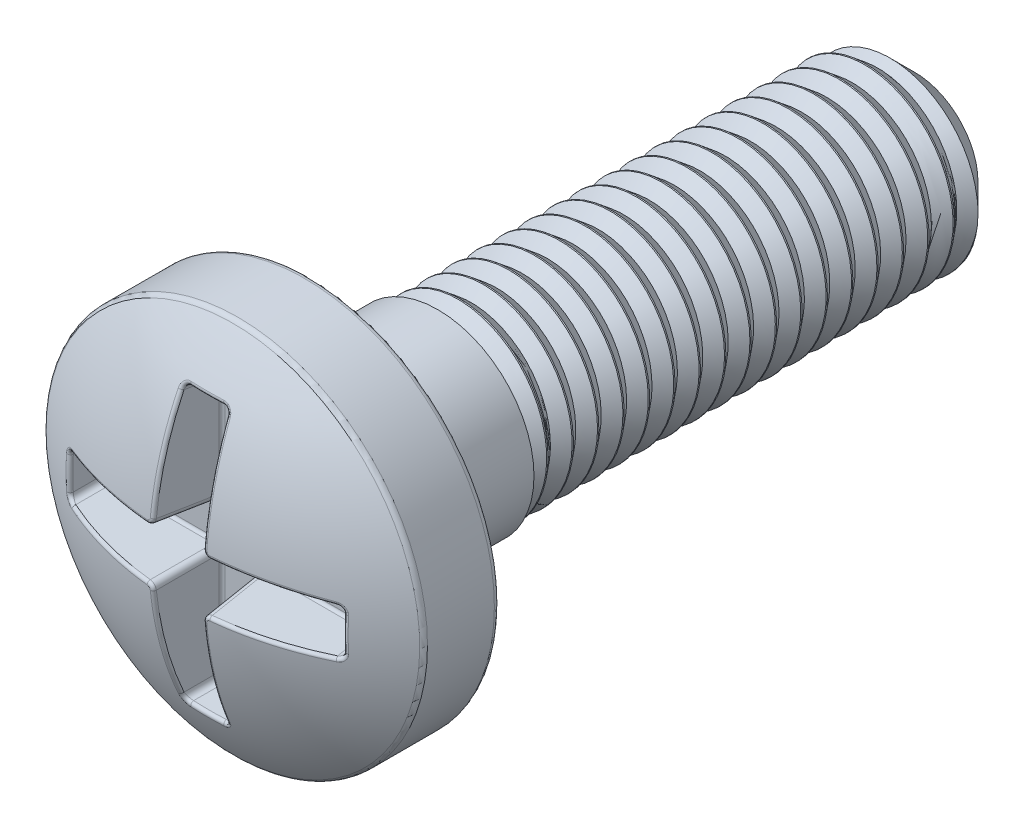
SolidWorks part; units mm, degrees
material "Cast Stainless Steel"
ref_plane "Front Plane" through (0, 0, 0) normal (0, 0, 1) x (1, 0, 0)
ref_plane "Top Plane" through (0, 0, 0) normal (0, 1, 0) x (1, 0, 0)
ref_plane "Right Plane" through (0, 0, 0) normal (1, 0, 0) x (0, 0, -1)
sketch "Sketch1" plane through (0, 0, 0) normal (1, 0, 0) x (0, 0, -1)
  line L0 (18.4658, 0) -> (18.4658, 2.4003)
  line L1 (0, 0) -> (18.4658, 0) construction
  line L2 (0, 0) -> (18.4658, 0)
  line L3 (18.4658, 2.4003) -> (3.3782, 2.4003)
  line L4 (3.3782, 2.4003) -> (3.3782, 4.7371)
  line L5 (3.3782, 4.7371) -> (1.4732, 4.7371)
  line L6 (0, 0) -> (0, -1.4058) construction
  arc A0 (0, 0) -> (1.4732, 4.7371) centre (8.3527, 0) cw
  dimension "D1" = 3.3782
  dimension "D2" = 9.4742
  dimension "D3" = 4.8006
  dimension "D4" = 1.905
  dimension "D5" = 15.0876
revolve "Revolve1" add sketch "Sketch1" angle 360 about L2
chamfer "Chamfer1" distance 0.8128 angle 45 1 edges at (2.4003, 0, -18.4658)
ref_plane "Plane1" through (0, 0, -6.5532) normal (0, 0, -1) x (-1, 0, 0)
sketch "Sketch2" plane through (0, 0, -6.5532) normal (0, 0, -1) x (-1, 0, 0)
  circle A0 centre (0, 0) radius 3.0006
  circle A2 centre (0, 0) radius 2.2733
  circle A3 centre (0, 0) radius 2.2733
  dimension "D1" = 0.127
extrude "Extrude1" cut sketch "Sketch2" along normal blind 14.224
sketch "Sketch3" plane through (0, 0, -6.5532) normal (0, 0, -1) x (-1, 0, 0)
  circle A0 centre (0, 0) radius 2.2733 construction
  circle A1 centre (0, 0) radius 2.2733
curve "Helix/Spiral1" pitch 0.635 height 12.3825 turns 19.5
sketch "Sketch4" plane through (0, 0, 0) normal (1, 0, 0) x (0, 0, -1)
  line L0 (6.5532, 2.2733) -> (6.8543, 2.0312)
  line L1 (6.8543, 2.0312) -> (7.1553, 2.2733)
  line L2 (17.78, 2.2733) -> (6.5532, 2.2733) construction
  line L3 (7.1553, 2.2733) -> (6.5532, 2.2733)
  line L4 (17.78, 2.2733) -> (6.5532, 2.2733) construction
sweep "Cut-Sweep1" cut profiles "Sketch4" path "Helix/Spiral1"
sketch "Sketch5" plane through (0, 0, -6.5532) normal (0, 0, -1) x (-1, 0, 0)
  circle A0 centre (0, 0) radius 2.4003 construction
  circle A1 centre (0, 0) radius 2.4003
extrude "Extrude2" add sketch "Sketch5" against normal blind 2.54
sketch "Sketch6" plane through (0, 0, 0) normal (0, 0, 1) x (1, 0, 0)
  line L0 (-4.7371, 0) -> (4.7371, 0) construction
  line L1 (0, 4.7371) -> (0, -4.7371) construction
  line L2 (-0.635, 0.635) -> (-0.635, 3.4925)
  line L3 (-0.635, -3.4925) -> (0.635, -3.4925)
  line L4 (-0.635, -3.4925) -> (-0.635, -0.635)
  line L5 (-0.635, 3.4925) -> (0.635, 3.4925)
  line L6 (0.635, -3.4925) -> (0.635, -0.635)
  line L7 (-3.4925, -0.635) -> (-0.635, -0.635)
  line L8 (-3.4925, -0.635) -> (-3.4925, 0.635)
  line L9 (-3.4925, 0.635) -> (-0.635, 0.635)
  line L10 (3.4925, -0.635) -> (3.4925, 0.635)
  line L11 (0.635, 0.635) -> (3.4925, 0.635)
  line L12 (0.635, 0.635) -> (0.635, 3.4925)
  line L13 (0.635, -0.635) -> (3.4925, -0.635)
  circle A0 centre (0, 0) radius 4.7371 construction
  dimension "D1" = 1.27
  dimension "D2" = 6.985
  dimension "D3" = 6.985
extrude "Extrude3" cut sketch "Sketch6" against normal blind 1.651 draft 5
fillet "Fillet1" radius 0.1524 14 edges at (-0.5297, -3.3872, -1.2037) (-3.3872, 0.5297, -1.2037) (-3.3872, -0.5297, -1.2037) (-0.5607, -0.5607, -0.8494) (0.5297, -3.3872, -1.2037) (0.5607, -0.5607, -0.8494) (3.3872, -0.5297, -1.2037) (3.3872, 0.5297, -1.2037) (0.5607, 0.5607, -0.8494) (0.5297, 3.3872, -1.2037) (-0.5297, 3.3872, -1.2037) (-0.5607, 0.5607, -0.8494) (4.7371, 0, -3.3782) (4.7371, 0, -1.4732)
fillet "Fillet2" radius 0.0762 48 edges at (-0.6867, 0.6637, -0.0548) (-2.0554, 0.6105, -0.2799) (-3.3968, 0.5107, -0.739) (-3.4281, 0, -0.7359) (-3.3761, -0.534, -0.7314) (-2.0554, -0.6105, -0.2799) (-0.6637, -0.6867, -0.0548) (-0.6105, -2.0554, -0.2799) (-0.5107, -3.3968, -0.739) (0, -3.4281, -0.7359) (0.534, -3.3761, -0.7314) (0.6105, -2.0554, -0.2799) (0.6867, -0.6637, -0.0548) (2.0554, -0.6105, -0.2799) (3.3968, -0.5107, -0.739) (3.4281, 0, -0.7359) (3.3761, 0.534, -0.7314) (2.0554, 0.6105, -0.2799) (0.6637, 0.6867, -0.0548) (0.6105, 2.0554, -0.2799) (0.5107, 3.3968, -0.739) (0, 3.4281, -0.7359) (-0.534, 3.3761, -0.7314) (-0.4462, 3.3037, -1.651) (0, 3.3481, -1.651) (0.4462, 3.3037, -1.651) (0.4906, 1.9193, -1.651) (0.535, 0.535, -1.651) (1.9193, 0.4906, -1.651) (3.3037, 0.4462, -1.651) (3.3481, 0, -1.651) (3.3037, -0.4462, -1.651) (1.9193, -0.4906, -1.651) (0.535, -0.535, -1.651) (0.4906, -1.9193, -1.651) (0.4462, -3.3037, -1.651) (0, -3.3481, -1.651) (-0.4462, -3.3037, -1.651) (-0.4906, -1.9193, -1.651) (-0.535, -0.535, -1.651) (-1.9193, -0.4906, -1.651) (-3.3037, -0.4462, -1.651) (-3.3481, 0, -1.651) (-3.3037, 0.4462, -1.651) (-1.9193, 0.4906, -1.651) (-0.535, 0.535, -1.651) (-0.6105, 2.0554, -0.2799) (-0.4906, 1.9193, -1.651)
